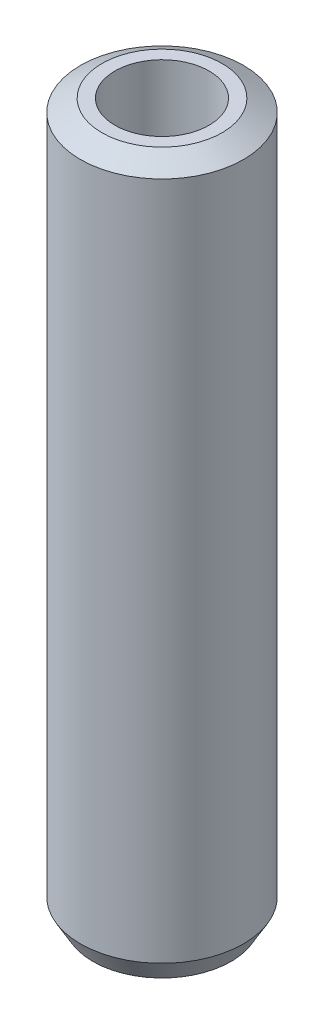
SolidWorks part; units mm, degrees
ref_plane "Front Plane" through (0, 0, 0) normal (0, 0, 1) x (1, 0, 0)
ref_plane "Top Plane" through (0, 0, 0) normal (0, 1, 0) x (1, 0, 0)
ref_plane "Right Plane" through (0, 0, 0) normal (1, 0, 0) x (0, 0, -1)
sketch "Sketch1" plane through (0, 0, 0) normal (0, 1, 0) x (1, 0, 0)
  circle A0 centre (0, 0) radius 30
  dimension "SHAFT_OD" = 60
extrude "Boss-Extrude1" add sketch "Sketch1" along normal blind 262.3632
sketch "Sketch2" plane through (0, 0, 0) normal (0, 1, 0) x (1, 0, 0)
  circle A0 centre (0, 0) radius 17.3195
  dimension "BORE_D" = 34.6389
extrude "Cut-Extrude1" cut sketch "Sketch2" along normal through all
chamfer "Chamfer1" distance 4.5668 angle 60 2 edges at (0, 262.3632, 30) (0, 0, 30) first distance on face at (0, 262.3632, 30) first distance on face at (0, 0, 17.3195)
